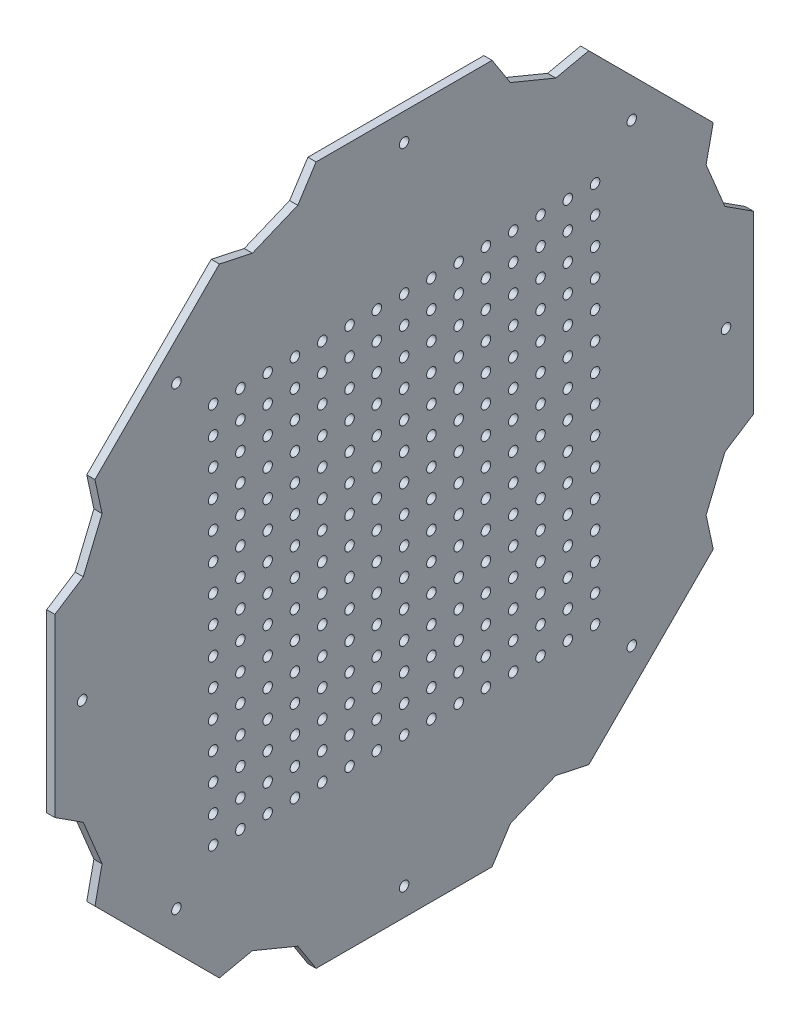
SolidWorks part; units mm, degrees
material "Акрил (Средняя-высокая ударопрочность)"
ref_plane "Спереди" through (0, 0, 0) normal (0, 0, 1) x (1, 0, 0)
ref_plane "Сверху" through (0, 0, 0) normal (0, 1, 0) x (1, 0, 0)
ref_plane "Справа" through (0, 0, 0) normal (1, 0, 0) x (0, 0, -1)
sketch "Эскиз1" plane through (0, 0, 0) normal (1, 0, 0) x (0, 0, -1)
  line L1 (128, -53.0193) -> (128, 53.0193)
  line L2 (128, 53.0193) -> (67.7055, 113.3139)
  line L3 (32.25, 128) -> (-53.0193, 128)
  line L4 (-53.0193, 128) -> (-128, 53.0193)
  line L5 (-128, 53.0193) -> (-128, -53.0193)
  line L6 (-128, -53.0193) -> (-53.0193, -128)
  line L7 (-53.0193, -128) -> (53.0193, -128)
  line L8 (53.0193, -128) -> (128, -53.0193)
  line L9 (-53.0193, 128) -> (32.25, 128)
  line L10 (67.7055, 113.3139) -> (128, 53.0193)
  line L11 (113.3139, 67.7055) -> (110.6977, 55.594)
  line L12 (110.6977, 55.594) -> (117.586, 38.9642)
  line L13 (38.9642, 117.586) -> (55.594, 110.6977)
  line L14 (55.594, 110.6977) -> (67.7055, 113.3139)
  line L15 (32.25, 128) -> (38.9642, 117.586)
  line L16 (117.586, 38.9642) -> (128, 32.25)
  line L17 (128, -32.25) -> (117.586, -38.9642)
  line L18 (117.586, -38.9642) -> (110.6977, -55.594)
  line L19 (110.6977, -55.594) -> (113.3139, -67.7055)
  line L20 (67.7055, -113.3139) -> (55.594, -110.6977)
  line L21 (55.594, -110.6977) -> (38.9642, -117.586)
  line L22 (38.9642, -117.586) -> (32.25, -128)
  line L23 (-32.25, -128) -> (-38.9642, -117.586)
  line L24 (-38.9642, -117.586) -> (-55.594, -110.6977)
  line L25 (-55.594, -110.6977) -> (-67.7055, -113.3139)
  line L26 (-113.3139, -67.7055) -> (-110.6977, -55.594)
  line L27 (-110.6977, -55.594) -> (-117.586, -38.9642)
  line L28 (-117.586, -38.9642) -> (-128, -32.25)
  line L29 (-128, 32.25) -> (-117.586, 38.9642)
  line L30 (-117.586, 38.9642) -> (-110.6977, 55.594)
  line L31 (-110.6977, 55.594) -> (-113.3139, 67.7055)
  line L32 (-67.7055, 113.3139) -> (-55.594, 110.6977)
  line L33 (-55.594, 110.6977) -> (-38.9642, 117.586)
  line L34 (-38.9642, 117.586) -> (-32.25, 128)
  line L35 (-128, 0) -> (-118, 0)
  arc A0 (48.9835, 118.2566) -> (61.8709, 112.0535) centre (0, 0) ccw construction
  circle A1 centre (-118, 0) radius 1.75
  circle A2 centre (-83.4386, 83.4386) radius 1.75
  circle A3 centre (0, 118) radius 1.75
  circle A4 centre (83.4386, 83.4386) radius 1.75
  circle A5 centre (118, 0) radius 1.75
  circle A6 centre (83.4386, -83.4386) radius 1.75
  circle A7 centre (0, -118) radius 1.75
  circle A8 centre (-83.4386, -83.4386) radius 1.75
  circle A9 centre (0, 0) radius 1.75
  circle A10 centre (10, 0) radius 1.75
  circle A11 centre (20, 0) radius 1.75
  circle A12 centre (30, 0) radius 1.75
  circle A13 centre (40, 0) radius 1.75
  circle A14 centre (50, 0) radius 1.75
  circle A15 centre (60, 0) radius 1.75
  circle A16 centre (70, 0) radius 1.75
  circle A17 centre (10, 10) radius 1.75
  circle A18 centre (20, 10) radius 1.75
  circle A19 centre (30, 10) radius 1.75
  circle A20 centre (40, 10) radius 1.75
  circle A21 centre (50, 10) radius 1.75
  circle A22 centre (60, 10) radius 1.75
  circle A23 centre (70, 10) radius 1.75
  circle A24 centre (10, 20) radius 1.75
  circle A25 centre (20, 20) radius 1.75
  circle A26 centre (30, 20) radius 1.75
  circle A27 centre (40, 20) radius 1.75
  circle A28 centre (50, 20) radius 1.75
  circle A29 centre (60, 20) radius 1.75
  circle A30 centre (70, 20) radius 1.75
  circle A31 centre (10, 30) radius 1.75
  circle A32 centre (20, 30) radius 1.75
  circle A33 centre (30, 30) radius 1.75
  circle A34 centre (40, 30) radius 1.75
  circle A35 centre (50, 30) radius 1.75
  circle A36 centre (60, 30) radius 1.75
  circle A37 centre (70, 30) radius 1.75
  circle A38 centre (10, 40) radius 1.75
  circle A39 centre (20, 40) radius 1.75
  circle A40 centre (30, 40) radius 1.75
  circle A41 centre (40, 40) radius 1.75
  circle A42 centre (50, 40) radius 1.75
  circle A43 centre (60, 40) radius 1.75
  circle A44 centre (70, 40) radius 1.75
  circle A45 centre (10, 50) radius 1.75
  circle A46 centre (20, 50) radius 1.75
  circle A47 centre (30, 50) radius 1.75
  circle A48 centre (40, 50) radius 1.75
  circle A49 centre (50, 50) radius 1.75
  circle A50 centre (60, 50) radius 1.75
  circle A51 centre (70, 50) radius 1.75
  circle A52 centre (10, 60) radius 1.75
  circle A53 centre (20, 60) radius 1.75
  circle A54 centre (30, 60) radius 1.75
  circle A55 centre (40, 60) radius 1.75
  circle A56 centre (50, 60) radius 1.75
  circle A57 centre (60, 60) radius 1.75
  circle A58 centre (70, 60) radius 1.75
  circle A59 centre (10, 70) radius 1.75
  circle A60 centre (20, 70) radius 1.75
  circle A61 centre (30, 70) radius 1.75
  circle A62 centre (40, 70) radius 1.75
  circle A63 centre (50, 70) radius 1.75
  circle A64 centre (60, 70) radius 1.75
  circle A65 centre (70, 70) radius 1.75
  circle A66 centre (0, 10) radius 1.75
  circle A67 centre (0, 20) radius 1.75
  circle A68 centre (0, 30) radius 1.75
  circle A69 centre (0, 40) radius 1.75
  circle A70 centre (0, 50) radius 1.75
  circle A71 centre (0, 60) radius 1.75
  circle A72 centre (0, 70) radius 1.75
  circle A73 centre (60, 70) radius 1.75
  circle A74 centre (50, 70) radius 1.75
  circle A75 centre (40, 70) radius 1.75
  circle A76 centre (30, 70) radius 1.75
  circle A77 centre (20, 70) radius 1.75
  circle A78 centre (10, 70) radius 1.75
  circle A79 centre (0, 70) radius 1.75
  circle A80 centre (-10, 70) radius 1.75
  circle A81 centre (-20, 70) radius 1.75
  circle A82 centre (-30, 70) radius 1.75
  circle A83 centre (-40, 70) radius 1.75
  circle A84 centre (-50, 70) radius 1.75
  circle A85 centre (-60, 70) radius 1.75
  circle A86 centre (-70, 70) radius 1.75
  circle A87 centre (60, 60) radius 1.75
  circle A88 centre (50, 60) radius 1.75
  circle A89 centre (40, 60) radius 1.75
  circle A90 centre (30, 60) radius 1.75
  circle A91 centre (20, 60) radius 1.75
  circle A92 centre (10, 60) radius 1.75
  circle A93 centre (0, 60) radius 1.75
  circle A94 centre (-10, 60) radius 1.75
  circle A95 centre (-20, 60) radius 1.75
  circle A96 centre (-30, 60) radius 1.75
  circle A97 centre (-40, 60) radius 1.75
  circle A98 centre (-50, 60) radius 1.75
  circle A99 centre (-60, 60) radius 1.75
  circle A100 centre (-70, 60) radius 1.75
  circle A101 centre (60, 50) radius 1.75
  circle A102 centre (50, 50) radius 1.75
  circle A103 centre (40, 50) radius 1.75
  circle A104 centre (30, 50) radius 1.75
  circle A105 centre (20, 50) radius 1.75
  circle A106 centre (10, 50) radius 1.75
  circle A107 centre (0, 50) radius 1.75
  circle A108 centre (-10, 50) radius 1.75
  circle A109 centre (-20, 50) radius 1.75
  circle A110 centre (-30, 50) radius 1.75
  circle A111 centre (-40, 50) radius 1.75
  circle A112 centre (-50, 50) radius 1.75
  circle A113 centre (-60, 50) radius 1.75
  circle A114 centre (-70, 50) radius 1.75
  circle A115 centre (60, 40) radius 1.75
  circle A116 centre (50, 40) radius 1.75
  circle A117 centre (40, 40) radius 1.75
  circle A118 centre (30, 40) radius 1.75
  circle A119 centre (20, 40) radius 1.75
  circle A120 centre (10, 40) radius 1.75
  circle A121 centre (0, 40) radius 1.75
  circle A122 centre (-10, 40) radius 1.75
  circle A123 centre (-20, 40) radius 1.75
  circle A124 centre (-30, 40) radius 1.75
  circle A125 centre (-40, 40) radius 1.75
  circle A126 centre (-50, 40) radius 1.75
  circle A127 centre (-60, 40) radius 1.75
  circle A128 centre (-70, 40) radius 1.75
  circle A129 centre (60, 30) radius 1.75
  circle A130 centre (50, 30) radius 1.75
  circle A131 centre (40, 30) radius 1.75
  circle A132 centre (30, 30) radius 1.75
  circle A133 centre (20, 30) radius 1.75
  circle A134 centre (10, 30) radius 1.75
  circle A135 centre (0, 30) radius 1.75
  circle A136 centre (-10, 30) radius 1.75
  circle A137 centre (-20, 30) radius 1.75
  circle A138 centre (-30, 30) radius 1.75
  circle A139 centre (-40, 30) radius 1.75
  circle A140 centre (-50, 30) radius 1.75
  circle A141 centre (-60, 30) radius 1.75
  circle A142 centre (-70, 30) radius 1.75
  circle A143 centre (60, 20) radius 1.75
  circle A144 centre (50, 20) radius 1.75
  circle A145 centre (40, 20) radius 1.75
  circle A146 centre (30, 20) radius 1.75
  circle A147 centre (20, 20) radius 1.75
  circle A148 centre (10, 20) radius 1.75
  circle A149 centre (0, 20) radius 1.75
  circle A150 centre (-10, 20) radius 1.75
  circle A151 centre (-20, 20) radius 1.75
  circle A152 centre (-30, 20) radius 1.75
  circle A153 centre (-40, 20) radius 1.75
  circle A154 centre (-50, 20) radius 1.75
  circle A155 centre (-60, 20) radius 1.75
  circle A156 centre (-70, 20) radius 1.75
  circle A157 centre (60, 10) radius 1.75
  circle A158 centre (50, 10) radius 1.75
  circle A159 centre (40, 10) radius 1.75
  circle A160 centre (30, 10) radius 1.75
  circle A161 centre (20, 10) radius 1.75
  circle A162 centre (10, 10) radius 1.75
  circle A163 centre (0, 10) radius 1.75
  circle A164 centre (-10, 10) radius 1.75
  circle A165 centre (-20, 10) radius 1.75
  circle A166 centre (-30, 10) radius 1.75
  circle A167 centre (-40, 10) radius 1.75
  circle A168 centre (-50, 10) radius 1.75
  circle A169 centre (-60, 10) radius 1.75
  circle A170 centre (-70, 10) radius 1.75
  circle A171 centre (60, 0) radius 1.75
  circle A172 centre (50, 0) radius 1.75
  circle A173 centre (40, 0) radius 1.75
  circle A174 centre (30, 0) radius 1.75
  circle A175 centre (20, 0) radius 1.75
  circle A176 centre (10, 0) radius 1.75
  circle A177 centre (0, 0) radius 1.75
  circle A178 centre (-10, 0) radius 1.75
  circle A179 centre (-20, 0) radius 1.75
  circle A180 centre (-30, 0) radius 1.75
  circle A181 centre (-40, 0) radius 1.75
  circle A182 centre (-50, 0) radius 1.75
  circle A183 centre (-60, 0) radius 1.75
  circle A184 centre (-70, 0) radius 1.75
  circle A185 centre (60, -10) radius 1.75
  circle A186 centre (50, -10) radius 1.75
  circle A187 centre (40, -10) radius 1.75
  circle A188 centre (30, -10) radius 1.75
  circle A189 centre (20, -10) radius 1.75
  circle A190 centre (10, -10) radius 1.75
  circle A191 centre (0, -10) radius 1.75
  circle A192 centre (-10, -10) radius 1.75
  circle A193 centre (-20, -10) radius 1.75
  circle A194 centre (-30, -10) radius 1.75
  circle A195 centre (-40, -10) radius 1.75
  circle A196 centre (-50, -10) radius 1.75
  circle A197 centre (-60, -10) radius 1.75
  circle A198 centre (-70, -10) radius 1.75
  circle A199 centre (60, -20) radius 1.75
  circle A200 centre (50, -20) radius 1.75
  circle A201 centre (40, -20) radius 1.75
  circle A202 centre (30, -20) radius 1.75
  circle A203 centre (20, -20) radius 1.75
  circle A204 centre (10, -20) radius 1.75
  circle A205 centre (0, -20) radius 1.75
  circle A206 centre (-10, -20) radius 1.75
  circle A207 centre (-20, -20) radius 1.75
  circle A208 centre (-30, -20) radius 1.75
  circle A209 centre (-40, -20) radius 1.75
  circle A210 centre (-50, -20) radius 1.75
  circle A211 centre (-60, -20) radius 1.75
  circle A212 centre (-70, -20) radius 1.75
  circle A213 centre (60, -30) radius 1.75
  circle A214 centre (50, -30) radius 1.75
  circle A215 centre (40, -30) radius 1.75
  circle A216 centre (30, -30) radius 1.75
  circle A217 centre (20, -30) radius 1.75
  circle A218 centre (10, -30) radius 1.75
  circle A219 centre (0, -30) radius 1.75
  circle A220 centre (-10, -30) radius 1.75
  circle A221 centre (-20, -30) radius 1.75
  circle A222 centre (-30, -30) radius 1.75
  circle A223 centre (-40, -30) radius 1.75
  circle A224 centre (-50, -30) radius 1.75
  circle A225 centre (-60, -30) radius 1.75
  circle A226 centre (-70, -30) radius 1.75
  circle A227 centre (60, -40) radius 1.75
  circle A228 centre (50, -40) radius 1.75
  circle A229 centre (40, -40) radius 1.75
  circle A230 centre (30, -40) radius 1.75
  circle A231 centre (20, -40) radius 1.75
  circle A232 centre (10, -40) radius 1.75
  circle A233 centre (0, -40) radius 1.75
  circle A234 centre (-10, -40) radius 1.75
  circle A235 centre (-20, -40) radius 1.75
  circle A236 centre (-30, -40) radius 1.75
  circle A237 centre (-40, -40) radius 1.75
  circle A238 centre (-50, -40) radius 1.75
  circle A239 centre (-60, -40) radius 1.75
  circle A240 centre (-70, -40) radius 1.75
  circle A241 centre (60, -50) radius 1.75
  circle A242 centre (50, -50) radius 1.75
  circle A243 centre (40, -50) radius 1.75
  circle A244 centre (30, -50) radius 1.75
  circle A245 centre (20, -50) radius 1.75
  circle A246 centre (10, -50) radius 1.75
  circle A247 centre (0, -50) radius 1.75
  circle A248 centre (-10, -50) radius 1.75
  circle A249 centre (-20, -50) radius 1.75
  circle A250 centre (-30, -50) radius 1.75
  circle A251 centre (-40, -50) radius 1.75
  circle A252 centre (-50, -50) radius 1.75
  circle A253 centre (-60, -50) radius 1.75
  circle A254 centre (-70, -50) radius 1.75
  circle A255 centre (60, -60) radius 1.75
  circle A256 centre (50, -60) radius 1.75
  circle A257 centre (40, -60) radius 1.75
  circle A258 centre (30, -60) radius 1.75
  circle A259 centre (20, -60) radius 1.75
  circle A260 centre (10, -60) radius 1.75
  circle A261 centre (0, -60) radius 1.75
  circle A262 centre (-10, -60) radius 1.75
  circle A263 centre (-20, -60) radius 1.75
  circle A264 centre (-30, -60) radius 1.75
  circle A265 centre (-40, -60) radius 1.75
  circle A266 centre (-50, -60) radius 1.75
  circle A267 centre (-60, -60) radius 1.75
  circle A268 centre (-70, -60) radius 1.75
  circle A269 centre (60, -70) radius 1.75
  circle A270 centre (50, -70) radius 1.75
  circle A271 centre (40, -70) radius 1.75
  circle A272 centre (30, -70) radius 1.75
  circle A273 centre (20, -70) radius 1.75
  circle A274 centre (10, -70) radius 1.75
  circle A275 centre (0, -70) radius 1.75
  circle A276 centre (-10, -70) radius 1.75
  circle A277 centre (-20, -70) radius 1.75
  circle A278 centre (-30, -70) radius 1.75
  circle A279 centre (-40, -70) radius 1.75
  circle A280 centre (-50, -70) radius 1.75
  circle A281 centre (-60, -70) radius 1.75
  circle A282 centre (-70, -70) radius 1.75
  circle A283 centre (70, 60) radius 1.75
  circle A284 centre (70, 50) radius 1.75
  circle A285 centre (70, 40) radius 1.75
  circle A286 centre (70, 30) radius 1.75
  circle A287 centre (70, 20) radius 1.75
  circle A288 centre (70, 10) radius 1.75
  circle A289 centre (70, 0) radius 1.75
  circle A290 centre (70, -10) radius 1.75
  circle A291 centre (70, -20) radius 1.75
  circle A292 centre (70, -30) radius 1.75
  circle A293 centre (70, -40) radius 1.75
  circle A294 centre (70, -50) radius 1.75
  circle A295 centre (70, -60) radius 1.75
  circle A296 centre (70, -70) radius 1.75
  point P15 (-10.3847, 128)
  point P18 (97.8527, 83.1666)
  point P22 (47.2791, 114.1418)
  dimension "D3" = 8
  dimension "D4" = 8
  dimension "D1" = 256
  dimension "D2" = 8
  dimension "D5" = 8
  dimension "D6" = 15
  dimension "D7" = 15
extrude "Бобышка-Вытянуть1" add sketch "Эскиз1" along normal blind 1.5 and the other way blind 1.5 contours A1 L5 L28 L27 L26 L6 L25 L24 L23 L7 L22 L21 L20 L8 L19 L18 L17 L1 L16 L12 L11 L10 L14 L13 L15 L3 L34 L33 L32 L4 L31 L30 L29 A296 A295 A294 A293 A292 A291 A290 region at (0, -32.5643, -120.8312)
